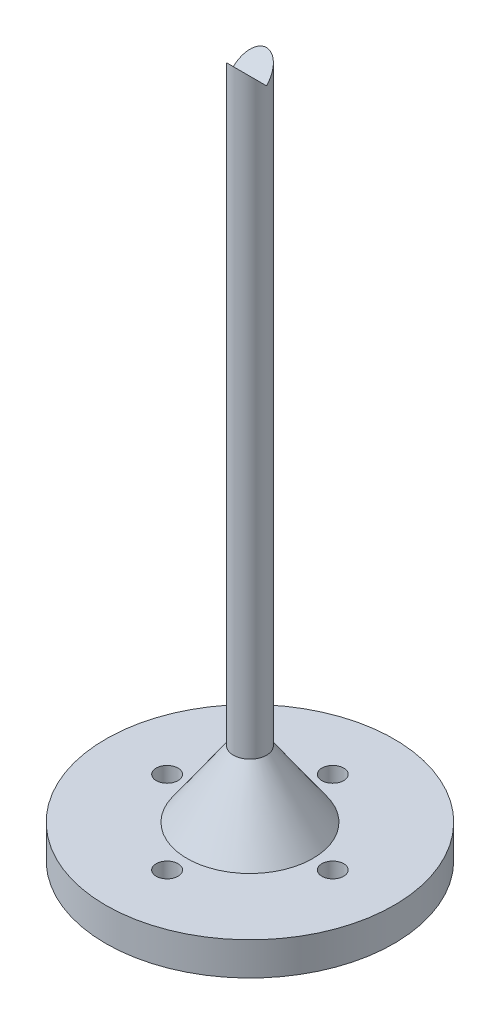
SolidWorks part; units mm, degrees
ref_plane "정면" through (0, 0, 0) normal (0, 0, 1) x (1, 0, 0)
ref_plane "윗면" through (0, 0, 0) normal (0, 1, 0) x (1, 0, 0)
ref_plane "우측면" through (0, 0, 0) normal (1, 0, 0) x (0, 0, -1)
sketch "Sketch1" plane through (0, 0, 0) normal (0, 1, 0) x (1, 0, 0)
  circle A0 centre (0, 0) radius 43.5
  circle A1 centre (0, 0) radius 25
  point P4 (25, 0)
extrude "Boss-Extrude4" add sketch "Sketch1" along normal blind 10 contours A0
sketch "Sketch10" plane through (0, 10, 0) normal (0, 1, 0) x (1, 0, 0)
  line L0 (0, 0) -> (0, -25)
  line L1 (0, 0) -> (25, 0)
  circle A0 centre (0, 0) radius 25
  point P5 (0, -25)
  dimension "D1" = 90
hole_wizard "M6 여유 구멍2" positions "Sketch16" profile "Sketch17" hole size "M6" standard "KS" end condition through all
sketch "Sketch16" plane through (0, 10, 0) normal (0, 1, 0) x (1, 0, 0)
  point P0 (0, -25)
sketch "Sketch17" plane through (0, 10, 25) normal (1, 0, 0) x (0, 0, 1)
  line L0 (0, 0) -> (0, 10)
  line L1 (0, 10) -> (3.3, 10)
  line L2 (3.3, 10) -> (3.3, 0)
  line L5 (3.3, 0) -> (0, 0)
  line L11 (0, -6.35) -> (0, 107.95) construction
  dimension "관통 구멍 지름" = 6.6
  dimension "관통 구멍 깊이" = 10
pattern_circular "CirPattern1" count 4 over 360 about axis through (0, 10, 0) along (0, -1, 0) of "M6 여유 구멍2"
sketch "Sketch20" plane through (0, 10, 0) normal (0, 1, 0) x (1, 0, 0)
  circle A0 centre (0, 0) radius 5
extrude "Boss-Extrude6" add sketch "Sketch20" along normal blind 200 contours A0
sketch "스케치3" plane through (0, 210, 0) normal (0, 1, 0) x (1, 0, 0)
  circle A0 centre (0, 0) radius 4.2
sketch "스케치12" plane through (0, 0, 0) normal (1, 0, 0) x (0, 0, -1)
  line L0 (-5, 210) -> (5, 210)
  line L1 (0, 205) -> (5, 210)
  line L2 (0, 205) -> (-5, 210)
  point P0 (-5, 210)
  point P4 (0, 205)
  point P5 (0, 210)
extrude "컷-돌출1" cut sketch "스케치12" against normal blind 10 and the other way blind 10
sketch "스케치11" plane through (0, 10, 0) normal (0, 1, 0) x (1, 0, 0)
  circle A0 centre (0, 0) radius 14
chamfer "모따기1" distance 14 angle 55 1 edges at (0, 10, 5) first distance on face at (0, 10, 5)
